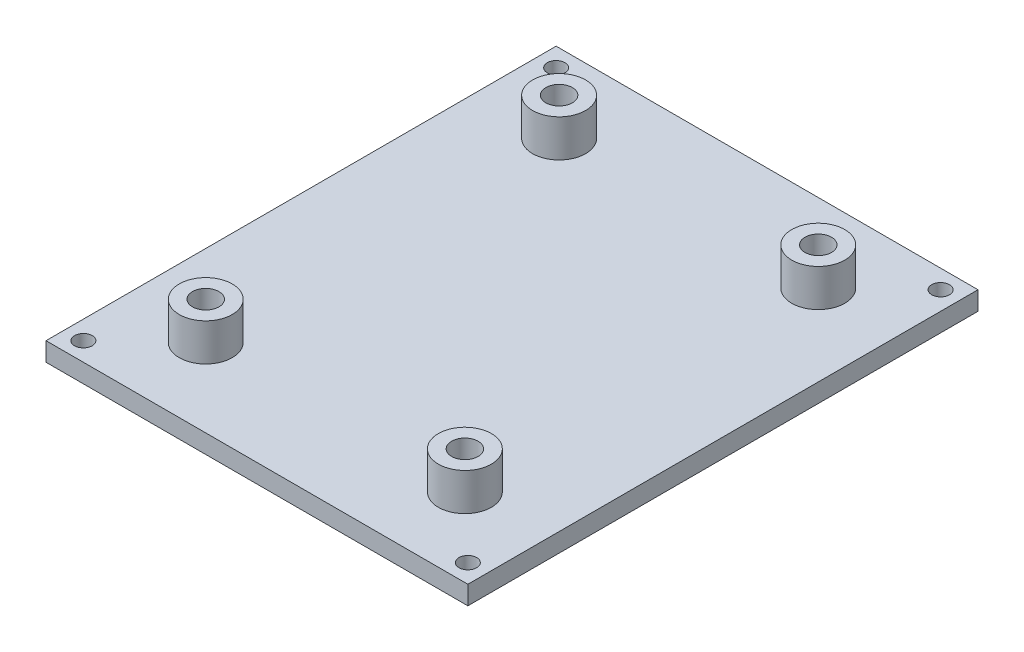
SolidWorks part; units mm, degrees
ref_plane "Front Plane" through (0, 0, 0) normal (0, 0, 1) x (1, 0, 0)
ref_plane "Top Plane" through (0, 0, 0) normal (0, 1, 0) x (1, 0, 0)
ref_plane "Right Plane" through (0, 0, 0) normal (1, 0, 0) x (0, 0, -1)
sketch "Sketch2" plane through (0, 0, 0) normal (0, 1, 0) x (1, 0, 0)
  line L0 (0, 43.307) -> (0, -43.307) construction
  line L1 (-35.814, 43.307) -> (35.814, 43.307)
  line L2 (-35.814, 43.307) -> (-35.814, -43.307)
  line L3 (-35.814, -43.307) -> (35.814, -43.307)
  line L4 (35.814, 43.307) -> (35.814, -43.307)
  line L9 (-35.814, 0) -> (35.814, 0) construction
  point P4 (0, 43.307)
  point P6 (-35.814, 0)
  dimension "D1" = 86.614
  dimension "D2" = 71.628
extrude "Boss-Extrude1" add sketch "Sketch2" along normal mid plane 3.175
sketch "Sketch3" plane through (0, 1.5875, 0) normal (0, 1, 0) x (1, 0, 0)
  line L0 (-35.814, 43.307) -> (-35.814, -43.307) construction
  line L5 (35.814, 43.307) -> (-35.814, 43.307) construction
  line L6 (0, 43.307) -> (0, -43.307) construction
  line L7 (-35.814, -43.307) -> (35.814, -43.307) construction
  line L8 (-35.814, 0) -> (35.814, 0) construction
  line L9 (35.814, -43.307) -> (35.814, 43.307) construction
  line L10 (-35.814, 43.307) -> (-29.464, 36.957) construction
  circle A0 centre (-32.639, 40.132) radius 1.5
  dimension "D5" = 3
extrude "Cut-Extrude1" cut sketch "Sketch3" against normal up to next
mirror "Mirror1" about plane through (0, 0, 0) normal (1, 0, 0) of "Cut-Extrude1" second plane through (0, 0, 0) second plane normal (0, 0, 1)
sketch "Sketch4" plane through (0, 1.5875, 0) normal (0, 1, 0) x (1, 0, 0)
  line L0 (35.814, 43.307) -> (-35.814, 43.307) construction
  line L5 (-35.814, -43.307) -> (35.814, -43.307) construction
  line L6 (35.814, -43.307) -> (35.814, 43.307) construction
  line L8 (-22, 30) -> (22, 30)
  line L9 (-22, 30) -> (-22, -30)
  line L10 (-22, -30) -> (22, -30)
  line L11 (22, 30) -> (22, -30)
  circle A4 centre (-22, 30) radius 4.5
  circle A5 centre (22, 30) radius 4.5
  circle A6 centre (22, -30) radius 4.5
  circle A7 centre (-22, -30) radius 4.5
  circle A8 centre (-22, 30) radius 2.25
  circle A9 centre (22, 30) radius 2.25
  circle A10 centre (22, -30) radius 2.25
  circle A11 centre (-22, -30) radius 2.25
  point P6 (0, 43.307)
  point P10 (0, -43.307)
  point P14 (35.814, 0)
  point P24 (0, 30)
  point P25 (22, 0)
  dimension "D5" = 9
  dimension "D1" = 9
  dimension "D2" = 9
  dimension "D6" = 9
  dimension "D7" = 4.5
  dimension "D8" = 4.5
  dimension "D9" = 4.5
  dimension "D10" = 4.5
  dimension "D3" = 60
  dimension "D4" = 44
extrude "Boss-Extrude2" add sketch "Sketch4" along normal blind 6.35 contours A8 L8 A4 L9 | A8 L9 A4 L8 | A9 L8 A5 L11 | A9 L11 A5 L8 | A10 L10 A6 L11 | A10 L11 A6 L10 | A11 L10 A7 L9 | A11 L9 A7 L10 region at (-23.681, 1.5875, -31.681) region at (-19.7718, 1.5875, -27.7718) region at (22, 1.5875, -34.3727) region at (19.7718, 1.5875, -27.7718) region at (-19.7718, 1.5875, 27.7718) region at (-22.1273, 1.5875, 26.625) region at (25.092, 1.5875, 26.908) region at (19.7718, 1.5875, 27.7718)
extrude "Boss-Extrude3" add sketch "Sketch4<3>" along normal blind 0.55 contours L9 A8 L8 | L8 A8 L9 | L8 A9 L11 | L11 A9 L8 | L10 A10 L11 | L11 A10 L10 | L9 A11 L10 | L10 A11 L9 region at (-22.3183, 1.5875, -30.3183) region at (-21.0451, 1.5875, -29.0451) region at (22.3183, 1.5875, -30.3183) region at (21.0451, 1.5875, -29.0451) region at (-21.0451, 1.5875, 29.0451) region at (-22.3183, 1.5875, 30.3183) region at (22.3183, 1.5875, 30.3183) region at (21.0451, 1.5875, 29.0451)
sketch "Sketch4<3>" plane through (0, 1.5875, 0) normal (0, 1, 0) x (1, 0, 0) same geometry as "Sketch4"
